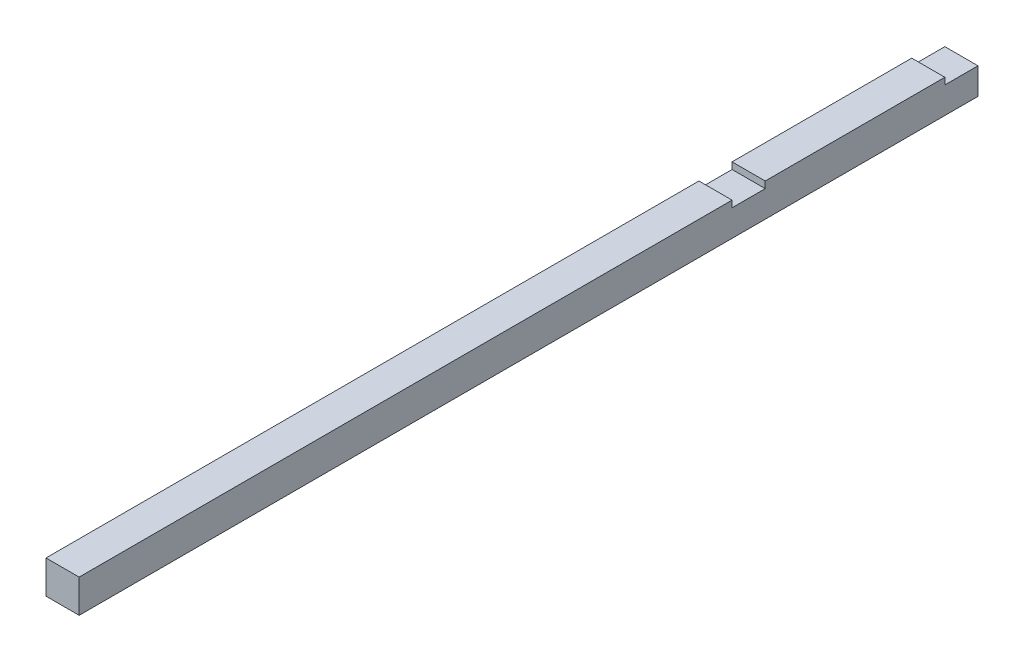
SolidWorks part; units mm, degrees
ref_plane "Plan de face" through (0, 0, 0) normal (0, 0, 1) x (1, 0, 0)
ref_plane "Plan de dessus" through (0, 0, 0) normal (0, 1, 0) x (1, 0, 0)
ref_plane "Plan de droite" through (0, 0, 0) normal (1, 0, 0) x (0, 0, -1)
sketch "Esquisse1" plane through (0, 0, 0) normal (0, 0, 1) x (1, 0, 0)
  line L0 (-5, 5) -> (5, -5) construction
  line L1 (-5, 5) -> (5, 5)
  line L2 (-5, 5) -> (-5, -5)
  line L3 (-5, -5) -> (5, -5)
  line L4 (5, 5) -> (5, -5)
  dimension "D1" = 10
extrude "Boss.-Extru.1" add sketch "Esquisse1" along normal offset from surface (310 mm away) 2 offset beyond the face yes
hole_wizard "Trou taraudé M6x1.01" positions "Esquisse3" profile "Esquisse2" tap size "M6x1.0" standard "Ansi Metric"
sketch "Esquisse3" plane through (0, 0, 0) normal (0, 0, -1) x (-1, 0, 0)
  point P0 (0, 0)
sketch "Esquisse2" plane through (0, 0, 0) normal (1, 0, 0) x (0, 1, 0)
  line L0 (0, 0) -> (0, 18.5022)
  line L1 (0, 18.5022) -> (2.5, 17)
  line L2 (2.5, 17) -> (2.5, 0.525)
  line L3 (2.5, 0.525) -> (3.025, 0)
  line L5 (3.025, 0) -> (0, 0)
  line L6 (-2.5, 0.525) -> (-3.025, 0) construction
  line L10 (0, 18.5022) -> (-2.5, 17) construction
  line L11 (0, -6.35) -> (0, 107.95) construction
  dimension "Diamètre du trou pour taraudage" = 5
  dimension "Profondeur du trou pour taraudage" = 17
  dimension "Diamètre du fraisage entrant" = 6.05
  dimension "Angle du fraisage entrant" = 90
  dimension "Angle de pointe" = 118
cosmetic thread "Filetage de perçage1" parameters "D1"=12, "D2"=6
sketch "Esquisse4" plane through (-5, 0, 0) normal (-1, 0, 0) x (0, 0, 1)
  line L0 (113, 3) -> (113, 239) construction
  line L1 (113, 3) -> (103, 3)
  line L2 (113, 3) -> (113, 5)
  line L3 (113, 5) -> (103, 5)
  line L4 (103, 3) -> (103, 5)
  line L5 (103, 3) -> (103, 239) construction
  line L6 (310, 5) -> (0, 5) construction
  dimension "D1" = 2
extrude "Enlèv. mat.-Extru.1" cut sketch "Esquisse4" against normal through all
sketch "Esquisse5" plane through (0, 5, 0) normal (0, 1, 0) x (1, 0, 0)
  line L0 (5, -310) -> (5, -113) construction
  line L1 (-5, 0) -> (5, 0)
  line L2 (-5, 0) -> (-5, -38.8)
  line L3 (-5, -38.8) -> (5, -38.8)
  line L4 (5, 0) -> (5, -38.8)
  line L5 (5, -103) -> (5, 0) construction
  line L7 (-51.4, -38.8) -> (26.6, -38.8) construction
extrude "Enlèv. mat.-Extru.2" cut sketch "Esquisse5" against normal through all
sketch "Esquisse6" plane through (5, 0, 0) normal (1, 0, 0) x (0, 0, -1)
  line L1 (-38.8, 5) -> (-48.8, 5)
  line L2 (-38.8, 5) -> (-38.8, 3)
  line L3 (-38.8, 3) -> (-48.8, 3)
  line L4 (-48.8, 5) -> (-48.8, 3)
extrude "Enlèv. mat.-Extru.3" cut sketch "Esquisse6" against normal through all
